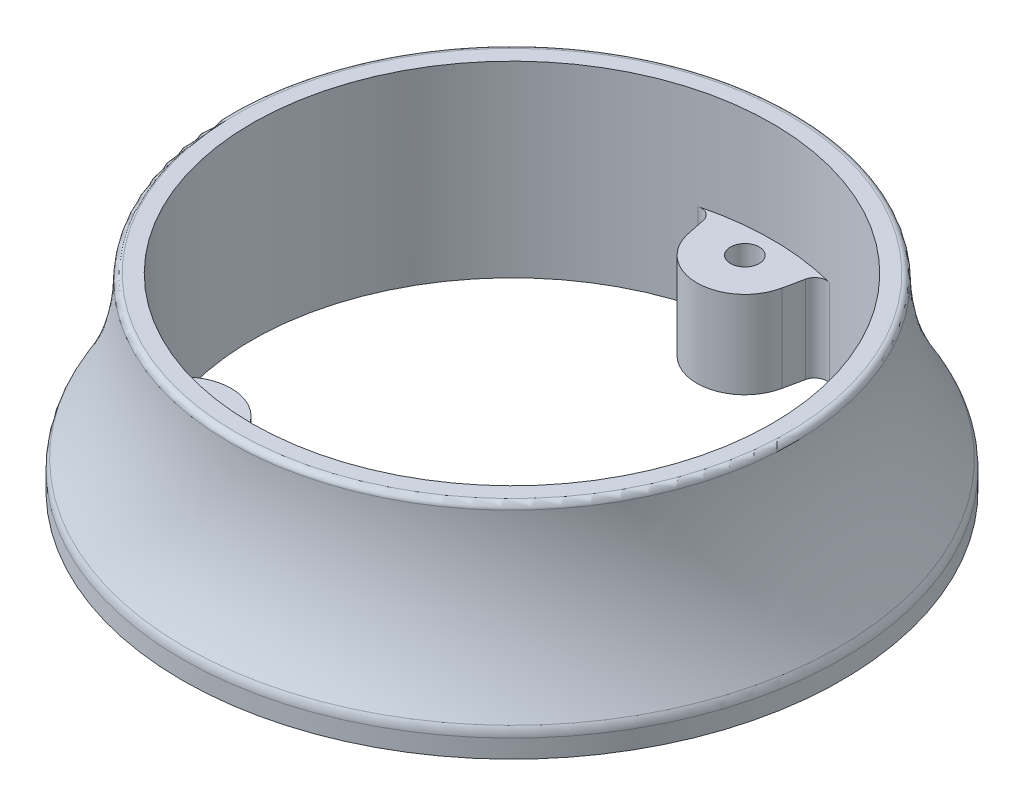
SolidWorks part; units mm, degrees
ref_plane "Ebene vorne" through (0, 0, 0) normal (0, 0, 1) x (1, 0, 0)
ref_plane "Ebene oben" through (0, 0, 0) normal (0, 1, 0) x (1, 0, 0)
ref_plane "Ebene rechts" through (0, 0, 0) normal (1, 0, 0) x (0, 0, -1)
sketch "Skizze1" plane through (0, 0, 0) normal (0, 1, 0) x (1, 0, 0)
  circle A0 centre (0, 0) radius 21.7
  circle A1 centre (0, 0) radius 23.5
extrude "Aufsatz-Linear austragen1" add sketch "Skizze1" along normal blind 8.4
sketch "Skizze2" plane through (0, 0, 0) normal (0, 1, 0) x (1, 0, 0)
  line L0 (-3.9145, 18.6075) -> (-4.2564, 20.233)
  line L1 (3.9145, 18.6075) -> (4.2564, 20.233)
  line L2 (-14.4417, -12.6076) -> (-15.5756, -13.5975)
  line L3 (-8.1947, -17.3309) -> (-8.8381, -18.6916)
  line L4 (8.1937, -17.3311) -> (8.8372, -18.6921)
  line L5 (14.4422, -12.6067) -> (15.5763, -13.5967)
  arc A0 (-5.4879, 20.9946) -> (-17.0175, -13.4646) centre (0, 0) ccw
  circle A1 centre (0, 0) radius 23.5
  circle A2 centre (0, 19.431) radius 1.2
  circle A3 centre (-11.811, -15.621) radius 1.2
  circle A4 centre (11.811, -15.621) radius 1.2
  arc A5 (-3.9145, 18.6075) -> (3.9145, 18.6075) centre (0, 19.431) ccw
  arc A6 (-8.1947, -17.3309) -> (-14.4417, -12.6076) centre (-11.811, -15.621) ccw
  arc A7 (14.4422, -12.6067) -> (8.1937, -17.3311) centre (11.811, -15.621) ccw
  arc A8 (-8.3174, -20.0427) -> (8.3164, -20.0432) centre (0, 0) ccw
  arc A9 (17.0181, -13.4638) -> (5.4879, 20.9946) centre (0, 0) ccw
  arc A10 (-4.2564, 20.233) -> (-5.4879, 20.9946) centre (-5.235, 20.0271) ccw
  arc A11 (4.2564, 20.233) -> (5.4879, 20.9946) centre (5.235, 20.0271) cw
  arc A12 (15.5763, -13.5967) -> (17.0181, -13.4638) centre (16.2339, -12.8433) ccw
  arc A13 (8.8372, -18.6921) -> (8.3164, -20.0432) centre (7.9331, -19.1195) cw
  arc A14 (-8.8381, -18.6916) -> (-8.3174, -20.0427) centre (-7.9341, -19.1191) ccw
  arc A15 (-15.5756, -13.5975) -> (-17.0175, -13.4646) centre (-16.2332, -12.8441) cw
  point P30 (16.3478, -14.2702)
  point P33 (9.2749, -19.618)
  point P36 (-9.2759, -19.6175)
  dimension "D1" = 1
extrude "Aufsatz-Linear austragen2" add sketch "Skizze2" against normal up to surface (7.2595 mm away)
sketch "Skizze3" plane through (0, 0, 0) normal (0, 0, 1) x (1, 0, 0)
  line L0 (0, 8.4) -> (0, -7.2595)
  line L1 (23.5, 8.4) -> (-23.5, 8.4) construction
  line L2 (-23.5, -7.2595) -> (23.5, -7.2595) construction
  line L3 (23.5, 8.4) -> (23.5, -7.2595)
  line L4 (23.5, -7.2595) -> (27.5, -7.2595)
  line L5 (27.5, -7.2595) -> (27.5, -5.7369)
  arc A0 (27.5, -5.7369) -> (27.2854, -4.9637) centre (26, -5.7369) ccw
  spline S0 degree 3 poles (23.5, 8.4) (23.5, 6.043) (24.1309, 1.4587) (26.0236, -2.8661) (27.2854, -4.9637) knots 0 0 0 0 0.4864 0.972801 0.972801 0.972801 0.972801
  dimension "D1" = 1.5
revolve "Rotation1" add sketch "Skizze3" angle 360 about L0 region at (24.9337, -3.269, 0)
fillet "Verrundung1" radius 0.5 1 edges at (0, 8.4, 23.5)
